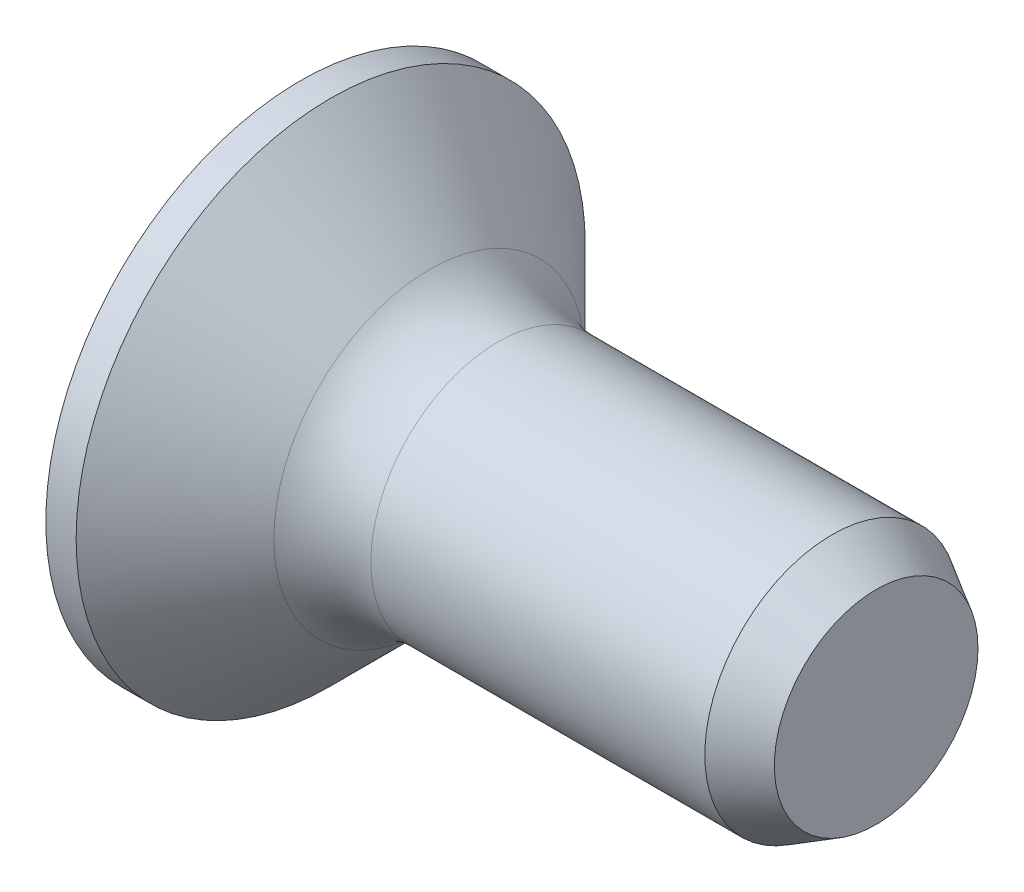
SolidWorks part; units mm, degrees
ref_plane "Front" through (0, 0, 0) normal (0, 0, 1) x (1, 0, 0)
ref_plane "Top" through (0, 0, 0) normal (0, 1, 0) x (1, 0, 0)
ref_plane "Right" through (0, 0, 0) normal (1, 0, 0) x (0, 0, -1)
sketch "Sketch1" plane through (0, 0, 0) normal (0, 0, 1) x (1, 0, 0)
  line L0 (0, 4.2) -> (0.5, 4.2)
  line L1 (0.5, 4.2) -> (2.6, 2.1)
  line L2 (2.6, 2.1) -> (9.5, 2.1)
  line L3 (9.5, 2.1) -> (9.5, 0)
  line L4 (9.5, 0) -> (0, 0)
  line L5 (0, 0) -> (0, 4.2)
  line L6 (6.6207, 0) -> (-0.9387, 0) construction
  dimension "D1" = 45
  dimension "k" = 2.6
revolve "Revolve1" add sketch "Sketch1" angle 360 about L6
cosmetic thread "ThreadCosmetic" [suppressed] parameters "D2"=3.2
chamfer "Chamfer1" distance 0.42 angle 60 1 edges at (9.5, 0, -2.1) first distance on face at (9.5, 0, -2.1)
sketch "Sketch9" plane through (0, 0, 0) normal (0, 0, 1) x (1, 0, 0)
  line L0 (3.8513, 1.6) -> (3.0287, 1.6)
  line L1 (3.0287, 1.6) -> (2.74, 2.1)
  line L2 (3.8513, 1.6) -> (4.14, 2.1)
  line L3 (2.74, 2.1) -> (2.74, 2.35)
  line L4 (4.14, 2.1) -> (4.14, 2.35)
  line L5 (2.74, 2.35) -> (4.14, 2.35)
  line L6 (3.44, 1.6) -> (3.44, 0) construction
  line L7 (0, 0) -> (7.3035, 0) construction
  line L8 (2.6, 2.1) -> (2.6, -2.1) construction
  line L9 (8.7725, 2.1) -> (2.6, 2.1) construction
  dimension "D2" = 60
  dimension "D3" = 0.25
  dimension "minordia" = 3.2
  dimension "threadstart" = 0.84
revolve "ThreadSchematic" [suppressed] cut sketch "Sketch9" angle 360 about L7
pattern_linear "ThdSchPat" [suppressed] count 5 spacing 1.4 along (1, 0, 0) of bodies 142
sketch "Sketch3" plane through (0, 0, 0) normal (0, 0, 1) x (1, 0, 0)
  line L0 (2.6, 2.1) -> (9.5, 2.1) construction
  line L2 (5.8, 2.1) -> (6.725, 2.1) construction
  line L3 (9.5, 2.1) -> (9.5, 0) construction
  line L4 (6.725, 2.1) -> (9.5, 2.1)
  line L5 (2.9, 0) -> (5.4301, 0) construction
  line L6 (9.5, 0) -> (9.7, 0)
  line L7 (9.7, 0) -> (9.7, 2.1)
  line L8 (9.7, 2.1) -> (9.5, 2.1)
  line L9 (6.725, 2.1) -> (9.5, 0)
  dimension "D1" = 0.925
revolve "EndCone" [suppressed] cut sketch "Sketch3" angle 360 about L5
sketch "Sketch4" plane through (0, 0, 0) normal (-1, 0, 0) x (0, 0, 1)
  line L0 (-0.575, 2.3) -> (-0.575, 0.575)
  line L1 (-0.575, 2.3) -> (0.575, 2.3)
  line L2 (-2.3, 0.575) -> (-2.3, -0.575)
  line L3 (-0.575, -2.3) -> (0.575, -2.3)
  line L4 (2.3, 0.575) -> (2.3, -0.575)
  line L5 (0.575, 2.3) -> (0.575, 0.575)
  line L6 (0.575, 0.575) -> (2.3, 0.575)
  line L7 (0.575, -0.575) -> (2.3, -0.575)
  line L8 (0.575, -0.575) -> (0.575, -2.3)
  line L9 (-0.575, -0.575) -> (-0.575, -2.3)
  line L10 (-0.575, -0.575) -> (-2.3, -0.575)
  line L11 (-0.575, 0.575) -> (-2.3, 0.575)
  line L12 (2.3, 0) -> (-2.3, 0) construction
  dimension "D1" = 1.15
extrude "Cut-Extrude1" cut sketch "Sketch4" against normal blind 2.1
draft "Draft1" type of draft neutral plane draft angle 35 faces to draft 4 face at (1.05, 0, 2.3) face at (1.05, 2.3, 0) face at (1.05, 0, -2.3) face at (1.05, -2.3, 0) neutral plane through (0, 0, 0) neutral plane normal (-1, 0, 0) parameters "D1"=35
draft "Draft2" type of draft neutral plane draft angle 8 faces to draft 8 face at (1.05, -1.0699, -0.575) face at (1.05, -0.575, -1.0699) face at (1.05, -0.575, 1.0699) face at (1.05, -1.0699, 0.575) face at (1.05, 1.0699, 0.575) face at (1.05, 0.575, 1.0699) face at (1.05, 0.575, -1.0699) face at (1.05, 1.0699, -0.575) neutral plane through (0, 0, 0) neutral plane normal (-1, 0, 0) parameters "D1"=8
sketch "Sketch6" plane through (2.1, 0, 0) normal (-1, 0, 0) x (0, 0, 1)
  line L0 (0.2799, 0.2799) -> (0.2799, 0.8296) construction
  line L1 (0.8296, 0.2799) -> (0.2799, 0.2799) construction
  line L2 (-0.2799, 0.8296) -> (-0.2799, 0.2799) construction
  line L3 (-0.2799, 0.2799) -> (-0.8296, 0.2799) construction
  line L4 (-0.8296, -0.2799) -> (-0.2799, -0.2799) construction
  line L5 (-0.2799, -0.2799) -> (-0.2799, -0.8296) construction
  line L6 (0.2799, -0.8296) -> (0.2799, -0.2799) construction
  line L7 (0.2799, -0.2799) -> (0.8296, -0.2799) construction
  line L9 (-0.5547, 0.2799) -> (-0.5547, -0.2799)
  line L10 (-0.2799, -0.5547) -> (0.2799, -0.5547)
  line L11 (0.5547, -0.2799) -> (0.5547, 0.2799)
  line L12 (0.2799, 0.5547) -> (-0.2799, 0.5547)
  arc A0 (0.2799, 0.5547) -> (0.5547, 0.2799) centre (0.5547, 0.5547) ccw
  arc A1 (-0.2799, 0.5547) -> (-0.5547, 0.2799) centre (-0.5547, 0.5547) cw
  arc A2 (-0.5547, -0.2799) -> (-0.2799, -0.5547) centre (-0.5547, -0.5547) cw
  arc A3 (0.2799, -0.5547) -> (0.5547, -0.2799) centre (0.5547, -0.5547) cw
sketch "Sketch7" plane through (0, 0, 0) normal (-1, 0, 0) x (0, 0, 1)
  line L8 (0.575, 0.575) -> (0.575, 2.3) construction
  line L9 (2.3, 0.575) -> (0.575, 0.575) construction
  line L10 (0.575, -0.575) -> (2.3, -0.575) construction
  line L11 (0.575, -2.3) -> (0.575, -0.575) construction
  line L12 (-0.575, 2.3) -> (-0.575, 0.575) construction
  line L13 (-0.575, 0.575) -> (-2.3, 0.575) construction
  line L14 (-2.3, -0.575) -> (-0.575, -0.575) construction
  line L15 (-0.575, -0.575) -> (-0.575, -2.3) construction
  line L16 (0.8498, 0.575) -> (0.8498, -0.575)
  line L17 (0.575, -0.8498) -> (-0.575, -0.8498)
  line L18 (-0.8498, -0.575) -> (-0.8498, 0.575)
  line L19 (-0.575, 0.8498) -> (0.575, 0.8498)
  arc A0 (0.575, 0.8498) -> (0.8498, 0.575) centre (0.8498, 0.8498) ccw
  arc A1 (-0.575, 0.8498) -> (-0.8498, 0.575) centre (-0.8498, 0.8498) cw
  arc A2 (-0.8498, -0.575) -> (-0.575, -0.8498) centre (-0.8498, -0.8498) cw
  arc A3 (0.2799, 0.5547) -> (0.5547, 0.2799) centre (0.5547, 0.5547) ccw construction
  arc A4 (0.8498, -0.575) -> (0.575, -0.8498) centre (0.8498, -0.8498) ccw
loft "Cut-Loft1" cut profiles "Sketch6", "Sketch7" connector at (2.1, 0.5547, 0.2799) connector at (0, 0.8498, 0.575)
sketch "Sketch8" plane through (0, 0, 0) normal (-1, 0, 0) x (0, 0, 1)
  line L0 (0, 0) -> (2.3, 2.3) construction
  line L1 (0.2799, 0.5547) -> (2.3, 2.3)
  line L2 (2.3, 2.3) -> (0.5547, 0.2799)
  line L3 (0.575, 2.3) -> (2.3, 2.3) construction
  line L4 (2.3, 2.3) -> (2.3, 0.575) construction
  line L5 (0, 0) -> (0.5547, 0) construction
  line L6 (0.5547, 0.2799) -> (0.5547, 0)
  line L7 (0.2799, 0.5547) -> (0, 0.5547)
  line L8 (0, 0.5547) -> (0, 0) construction
  line L9 (0.2799, -0.5547) -> (0, -0.5547)
  line L10 (2.3, -2.3) -> (0.2799, -0.5547)
  line L11 (0.5547, -0.2799) -> (2.3, -2.3)
  line L12 (0.5547, -0.2799) -> (0.5547, 0)
  line L13 (-0.5547, -0.2799) -> (-0.5547, 0)
  line L14 (-2.3, -2.3) -> (-0.5547, -0.2799)
  line L15 (-0.2799, -0.5547) -> (-2.3, -2.3)
  line L16 (-0.2799, -0.5547) -> (0, -0.5547)
  line L17 (-0.2799, 0.5547) -> (0, 0.5547)
  line L18 (-2.3, 2.3) -> (-0.2799, 0.5547)
  line L19 (-0.5547, 0.2799) -> (-2.3, 2.3)
  line L20 (-0.5547, 0.2799) -> (-0.5547, 0)
  arc A1 (0.2799, 0.5547) -> (0.5547, 0.2799) centre (0.5547, 0.5547) ccw construction
  arc A2 (0.2799, 0.5547) -> (0.5547, 0.2799) centre (0.5547, 0.5547) ccw construction
extrude "TypeZ" [suppressed] cut sketch "Sketch8" against normal blind 0.42 draft 3
fillet "Fillet1" radius 1.6 1 edges at (2.6, 0, -2.1)
equation "\"D1@Chamfer1\" = \"d@Sketch1\" / 10"
equation "\"D1@Sketch4\" = \"m@Sketch4\" / 4"
equation "\"D1@TypeZ\" = \"p@Cut-Extrude1\"*0.2"
equation "\"D1@Sketch3\" = \"y@Sketch3\" / 4"
equation "\"threadstart@Sketch9\"=\"advance@Sketch9\"*0.6"
equation "\"D1@ThdSchPat\" = int(((\"l@Sketch1\"-\"k@Sketch1\")/\"advance@Sketch9\") + 0.8)"
equation "\"D3@ThdSchPat\" = \"advance@Sketch9\""
equation "\"minordia@Sketch9\" = \"D2@ThreadCosmetic\""
